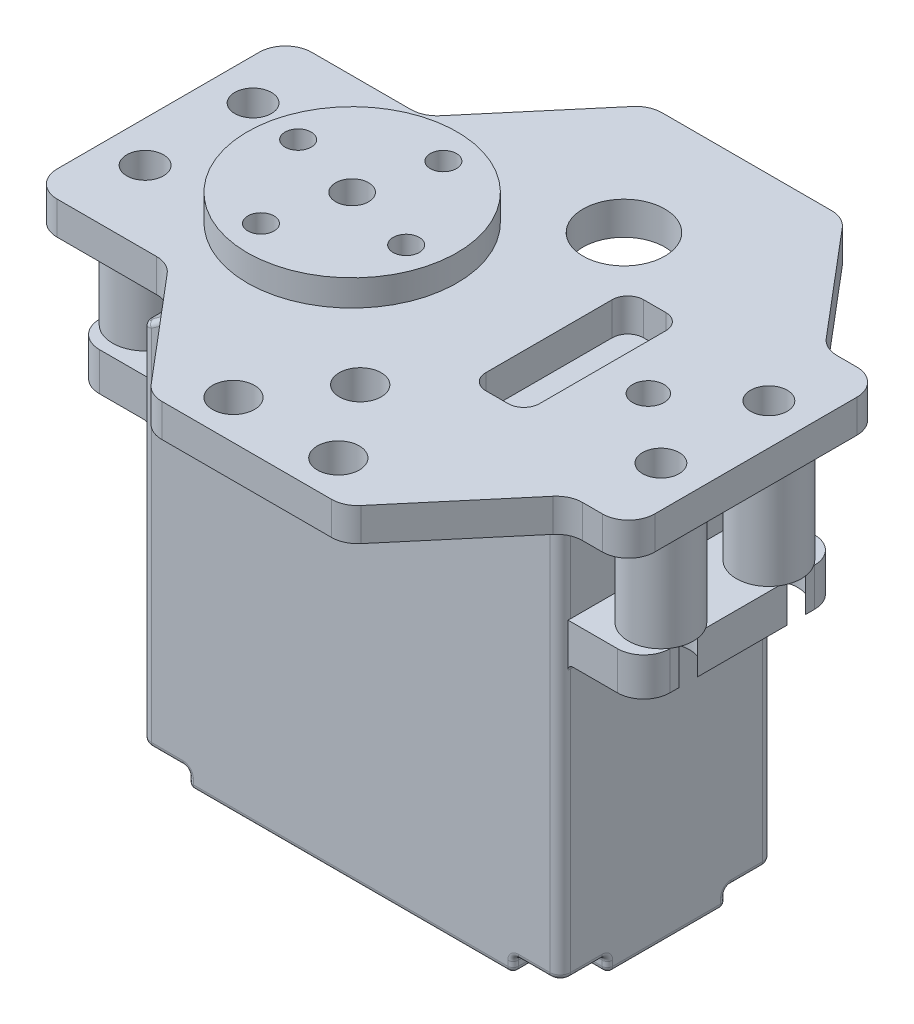
SolidWorks part; units mm, degrees
ref_plane "前基準面" through (0, 0, 0) normal (0, 0, 1) x (1, 0, 0)
ref_plane "上基準面" through (0, 0, 0) normal (0, 1, 0) x (1, 0, 0)
ref_plane "右基準面" through (0, 0, 0) normal (1, 0, 0) x (0, 0, -1)
sketch "草圖1" plane through (0, 0, 0) normal (0, 1, 0) x (1, 0, 0)
  line L0 (0, 23.4065) -> (0, -21.6093) construction
  line L1 (-8.0903, 23.85) -> (8.0903, 23.85)
  line L2 (9.999, 22.9646) -> (18.411, 13.0204)
  line L3 (20.3197, 12.135) -> (22.21, 12.135)
  line L4 (24.71, 9.635) -> (24.71, -9.635)
  line L5 (24.71, 0) -> (-24.71, 0) construction
  line L6 (-8.0903, -23.85) -> (8.0903, -23.85)
  line L7 (20.3197, -12.135) -> (22.21, -12.135)
  line L8 (9.999, -22.9646) -> (18.411, -13.0204)
  line L9 (-9.999, -22.9646) -> (-18.411, -13.0204)
  line L10 (-20.3197, -12.135) -> (-29.79, -12.135)
  line L11 (-32.29, 9.635) -> (-32.29, -9.635)
  line L12 (-20.3197, 12.135) -> (-29.79, 12.135)
  line L13 (-9.999, 22.9646) -> (-18.411, 13.0204)
  line L14 (5, -20.1095) -> (12.4142, -20.1095) construction
  line L15 (6.4847, -7.525) -> (8.61, -7.525)
  line L16 (4.9847, -6.025) -> (4.9847, 6.025)
  line L17 (6.4847, 7.525) -> (8.61, 7.525)
  line L18 (10.11, -6.025) -> (10.11, 6.025)
  line L19 (4.9847, -7.525) -> (10.11, 7.525) construction
  line L20 (4.9847, 7.525) -> (10.11, -7.525) construction
  arc A0 (-20.3197, 12.135) -> (-18.411, 13.0204) centre (-20.3197, 14.635) ccw
  arc A1 (-32.29, 9.635) -> (-29.79, 12.135) centre (-29.79, 9.635) cw
  arc A2 (-29.79, -12.135) -> (-32.29, -9.635) centre (-29.79, -9.635) cw
  arc A3 (-18.411, -13.0204) -> (-20.3197, -12.135) centre (-20.3197, -14.635) ccw
  arc A4 (-9.999, -22.9646) -> (-8.0903, -23.85) centre (-8.0903, -21.35) ccw
  arc A5 (8.0903, -23.85) -> (9.999, -22.9646) centre (8.0903, -21.35) ccw
  arc A6 (20.3197, -12.135) -> (18.411, -13.0204) centre (20.3197, -14.635) ccw
  arc A7 (18.411, 13.0204) -> (20.3197, 12.135) centre (20.3197, 14.635) ccw
  arc A8 (-9.999, 22.9646) -> (-8.0903, 23.85) centre (-8.0903, 21.35) cw
  arc A9 (8.0903, 23.85) -> (9.999, 22.9646) centre (8.0903, 21.35) cw
  arc A10 (22.21, 12.135) -> (24.71, 9.635) centre (22.21, 9.635) cw
  arc A11 (22.21, -12.135) -> (24.71, -9.635) centre (22.21, -9.635) ccw
  circle A12 centre (0, 12.135) radius 3.9
  arc A13 (8.61, -7.525) -> (10.11, -6.025) centre (8.61, -6.025) ccw
  arc A14 (6.4847, -7.525) -> (4.9847, -6.025) centre (6.4847, -6.025) cw
  arc A15 (4.9847, 6.025) -> (6.4847, 7.525) centre (6.4847, 6.025) cw
  arc A16 (8.61, 7.525) -> (10.11, 6.025) centre (8.61, 6.025) cw
  circle A17 centre (0, -13.0204) radius 2
  circle A18 centre (-5, -20.1095) radius 2
  circle A19 centre (5, -20.1095) radius 2
  point P3 (7.5474, 0)
  point P14 (0, -23.85)
  point P19 (0, 23.85)
  point P25 (-19.16, 12.135)
  point P30 (-32.29, -12.135)
  point P33 (-19.16, -12.135)
  point P36 (-9.25, -23.85)
  point P39 (9.25, -23.85)
  point P42 (19.16, -12.135)
  point P45 (19.16, 12.135)
  point P50 (9.25, 23.85)
  point P53 (24.71, 12.135)
  point P56 (24.71, -12.135)
  point P78 (0, 0)
  point P80 (4.9597, -20.1095)
  point P82 (4.9847, -20.09)
  dimension "D7" = 2.5
  dimension "D8" = 7.8
  dimension "D11" = 1.5
  dimension "D12" = 4
  dimension "D1" = 57
  dimension "D2" = 47.7
  dimension "D3" = 24.27
  dimension "D4" = 5.55
  dimension "D5" = 13.13
  dimension "D6" = 18.5
  dimension "D9" = 14.6
  dimension "D10" = 15.05
extrude "填料-伸長1" add sketch "草圖1" along normal blind 3.05 and the other way blind 0.1
sketch "草圖2" plane through (0, -0.1, 0) normal (0, -1, 0) x (1, 0, 0)
  line L0 (24.71, 9.635) -> (24.71, -9.635) construction
  line L1 (-32.29, -9.635) -> (-32.29, 9.635) construction
  line L2 (-25.2838, 0) -> (21.674, 0) construction
  circle A0 centre (20.81, 5.15) radius 3.1
  circle A1 centre (20.81, -5.15) radius 3.1
  circle A2 centre (-28.39, 5.15) radius 3.1
  circle A3 centre (-28.39, -5.15) radius 3.1
  dimension "D1" = 6.2
  dimension "D2" = 3.9
  dimension "D3" = 3.9
  dimension "D4" = 10.3
extrude "填料-伸長2" add sketch "草圖2" along normal blind 10
sketch "草圖3" plane through (0, -10.1, 0) normal (0, -1, 0) x (1, 0, 0)
  line L0 (-32.29, 0) -> (24.71, 0) construction
  line L1 (-28.4995, -9.4) -> (20.9195, -9.4)
  line L2 (-30.9995, -6.9) -> (-30.9995, -6.0177)
  line L3 (-28.4995, 9.4) -> (20.9195, 9.4)
  line L4 (23.4195, -6.9) -> (23.4195, -6.0177)
  line L5 (-30.9995, -9.4) -> (23.4195, 9.4) construction
  line L6 (-30.9995, 9.4) -> (23.4195, -9.4) construction
  line L7 (-32.29, -9.635) -> (-32.29, 9.635) construction
  line L8 (24.71, 9.635) -> (24.71, -9.635) construction
  line L9 (-3.79, 0) -> (-3.79, -23.85) construction
  line L10 (8.0903, -23.85) -> (-8.0903, -23.85) construction
  line L11 (23.4195, 6.0177) -> (23.4195, 6.9)
  line L12 (-30.9995, 6.0177) -> (-30.9995, 6.9)
  line L13 (-30.9995, -4.2823) -> (-30.9995, 4.2823)
  line L14 (23.4195, -4.2823) -> (23.4195, 4.2823)
  arc A0 (-30.9995, 4.2823) -> (-30.9995, 6.0177) centre (-28.39, 5.15) ccw
  arc A1 (23.4195, 6.0177) -> (23.4195, 4.2823) centre (20.81, 5.15) ccw
  arc A2 (23.4195, -4.2823) -> (23.4195, -6.0177) centre (20.81, -5.15) ccw
  arc A3 (-30.9995, -6.0177) -> (-30.9995, -4.2823) centre (-28.39, -5.15) ccw
  arc A4 (20.9195, -9.4) -> (23.4195, -6.9) centre (20.9195, -6.9) ccw
  arc A5 (-28.4995, -9.4) -> (-30.9995, -6.9) centre (-28.4995, -6.9) cw
  arc A6 (-30.9995, 6.9) -> (-28.4995, 9.4) centre (-28.4995, 6.9) cw
  arc A7 (20.9195, 9.4) -> (23.4195, 6.9) centre (20.9195, 6.9) cw
  point P0 (-3.79, 0)
  dimension "D2" = 5.5
  dimension "D3" = 2.5
  dimension "D1" = 18.8
extrude "填料-伸長3" add sketch "草圖3" along normal blind 3.65
sketch "草圖5" plane through (0, -13.75, 0) normal (0, -1, 0) x (1, 0, 0)
  line L0 (20.9195, 9.4) -> (-28.4995, 9.4) construction
  line L1 (-3.79, 9.4) -> (-3.79, -9.4) construction
  line L2 (-28.4995, -9.4) -> (20.9195, -9.4) construction
  line L3 (-85.4185, 0) -> (23.4195, 0) construction
  line L5 (23.4195, -4.2823) -> (23.4195, 4.2823) construction
  line L7 (-22.79, -10.15) -> (15.21, -10.15)
  line L8 (-23.79, -9.15) -> (-23.79, 9.15)
  line L9 (-22.79, 10.15) -> (15.21, 10.15)
  line L10 (16.21, -9.15) -> (16.21, 9.15)
  line L11 (-23.79, -10.15) -> (16.21, 10.15) construction
  line L12 (-23.79, 10.15) -> (16.21, -10.15) construction
  arc A0 (15.21, -10.15) -> (16.21, -9.15) centre (15.21, -9.15) ccw
  arc A1 (-22.79, -10.15) -> (-23.79, -9.15) centre (-22.79, -9.15) cw
  arc A2 (-23.79, 9.15) -> (-22.79, 10.15) centre (-22.79, 9.15) cw
  arc A3 (15.21, 10.15) -> (16.21, 9.15) centre (15.21, 9.15) cw
  point P6 (-3.79, 0)
  point P9 (-30.9995, 0)
  dimension "D3" = 1
  dimension "D1" = 20.3
  dimension "D2" = 40
extrude "填料-伸長4" add sketch "草圖5" along normal blind 27.57 and the other way blind 12.45
sketch "草圖6" plane through (0, -41.32, 0) normal (0, -1, 0) x (1, 0, 0)
  line L0 (11.71, 10.15) -> (11.71, 8.15)
  line L1 (15.21, 10.15) -> (-22.79, 10.15) construction
  line L2 (14.21, 5.65) -> (16.21, 5.65)
  line L3 (16.21, -9.15) -> (16.21, 9.15) construction
  line L4 (-23.79, 0) -> (16.21, 0) construction
  line L5 (-23.79, 9.15) -> (-23.79, -9.15) construction
  line L6 (16.21, -9.15) -> (16.21, 9.15) construction
  line L7 (11.71, -10.15) -> (11.71, -8.15)
  line L8 (-3.79, 10.15) -> (-3.79, -10.15) construction
  line L9 (-22.79, -10.15) -> (15.21, -10.15) construction
  line L10 (14.21, -5.65) -> (16.21, -5.65)
  line L11 (-19.29, -10.15) -> (-19.29, -8.15)
  line L12 (-21.79, -5.65) -> (-23.79, -5.65)
  line L13 (-19.29, 10.15) -> (-19.29, 8.15)
  line L14 (-21.79, 5.65) -> (-23.79, 5.65)
  line L15 (16.21, 5.65) -> (16.21, 9.15)
  line L16 (-19.29, 10.15) -> (-22.79, 10.15)
  line L17 (-23.79, -5.65) -> (-23.79, -9.15)
  line L18 (11.71, -10.15) -> (15.21, -10.15)
  line L19 (16.21, -9.15) -> (16.21, 9.15)
  line L20 (15.21, 10.15) -> (-22.79, 10.15)
  line L21 (-23.79, 9.15) -> (-23.79, -9.15)
  line L22 (-22.79, -10.15) -> (15.21, -10.15)
  line L23 (16.21, -9.15) -> (16.21, -5.65)
  line L24 (15.21, 10.15) -> (11.71, 10.15)
  line L25 (-23.79, 9.15) -> (-23.79, 5.65)
  line L26 (-22.79, -10.15) -> (-19.29, -10.15)
  arc A0 (11.71, 8.15) -> (14.21, 5.65) centre (14.21, 8.15) ccw
  arc A1 (11.71, -8.15) -> (14.21, -5.65) centre (14.21, -8.15) cw
  arc A2 (-19.29, -8.15) -> (-21.79, -5.65) centre (-21.79, -8.15) ccw
  arc A3 (-19.29, 8.15) -> (-21.79, 5.65) centre (-21.79, 8.15) cw
  arc A8 (15.21, -10.15) -> (16.21, -9.15) centre (15.21, -9.15) ccw
  arc A9 (16.21, 9.15) -> (15.21, 10.15) centre (15.21, 9.15) ccw
  arc A10 (-22.79, 10.15) -> (-23.79, 9.15) centre (-22.79, 9.15) ccw
  arc A11 (-23.79, -9.15) -> (-22.79, -10.15) centre (-22.79, -9.15) ccw
  arc A12 (15.21, -10.15) -> (16.21, -9.15) centre (15.21, -9.15) ccw
  arc A13 (16.21, 9.15) -> (15.21, 10.15) centre (15.21, 9.15) ccw
  arc A14 (-22.79, 10.15) -> (-23.79, 9.15) centre (-22.79, 9.15) ccw
  arc A15 (-23.79, -9.15) -> (-22.79, -10.15) centre (-22.79, -9.15) ccw
  point P9 (11.71, 5.65)
  dimension "D3" = 2.5
  dimension "D1" = 4.5
  dimension "D2" = 4.5
  dimension "D4" = 0
extrude "除料-伸長1" cut sketch "草圖6" against normal blind 1.5
sketch "草圖9" plane through (0, 0, 10.15) normal (0, 0, 1) x (1, 0, 0)
  line L0 (-18.29, -1.3) -> (-23.79, -5.2131)
  line L1 (15.21, -1.3) -> (-22.79, -1.3) construction
  line L2 (-23.79, -1.3) -> (-23.79, -10.1) construction
  line L3 (-23.79, -5.2131) -> (-23.79, -1.3)
  line L4 (-23.79, -1.3) -> (-18.29, -1.3)
  dimension "D1" = 5.5
  dimension "D2" = 6.75
extrude "除料-伸長3" cut sketch "草圖9" against normal through all
fillet "圓角1" radius 0.5 65 edges at (-23.782, -13.75, 9.276) (-23.782, -13.75, -9.276) (16.202, -13.75, -9.276) (16.202, -13.75, 9.276) (-23.79, -40.57, -5.65) (-23.79, -13.75, 0) (-23.79, -40.57, 5.65) (16.21, -40.57, 5.65) (16.21, -13.75, 0) (16.21, -40.57, -5.65) (15.9171, -39.82, 9.8571) (16.21, -39.82, 7.4) (15.21, -39.82, 5.65) (12.4422, -39.82, 6.3822) (11.71, -39.82, 9.15) (11.71, -39.82, -9.15) (12.4422, -39.82, -6.3822) (15.21, -39.82, -5.65) (16.21, -39.82, -7.4) (15.9171, -39.82, -9.8571) (-19.29, -39.82, 9.15) (-20.0222, -39.82, 6.3822) (-22.79, -39.82, 5.65) (-23.79, -39.82, 7.4) (-23.4971, -39.82, 9.8571) (13.46, -39.82, 10.15) (11.71, -40.57, 10.15) (-19.29, -40.57, 10.15) (-21.04, -39.82, 10.15) (-19.29, -40.57, -10.15) (11.71, -40.57, -10.15) (13.46, -39.82, -10.15) (-23.4971, -39.82, -9.8571) (-23.79, -39.82, -7.4) (-22.79, -39.82, -5.65) (-20.0222, -39.82, -6.3822) (-19.29, -39.82, -9.15) (-21.04, -39.82, -10.15) (-3.79, -41.32, 10.15) (11.71, -41.32, 9.15) (12.4422, -41.32, 6.3822) (15.21, -41.32, 5.65) (16.21, -41.32, 0) (15.21, -41.32, -5.65) (12.4422, -41.32, -6.3822) (11.71, -41.32, -9.15) (-3.79, -41.32, -10.15) (-19.29, -41.32, -9.15) (-20.0222, -41.32, -6.3822) (-22.79, -41.32, -5.65) (-23.79, -41.32, 0) (-22.79, -41.32, 5.65) (-20.0222, -41.32, 6.3822) (-19.29, -41.32, 9.15) (-23.79, -5.2131, 0) (-23.4971, -5.0047, -9.8571) (-20.54, -2.9008, -10.15) (-20.54, -2.9008, 10.15) (-23.4971, -5.0047, 9.8571) (15.9171, -1.3, -9.8571) (16.21, -1.3, 0) (15.9171, -1.3, 9.8571) (-1.54, -1.3, 10.15) (-18.29, -1.3, 0) (-1.54, -1.3, -10.15)
sketch "草圖11" plane through (0, 3.05, 0) normal (0, 1, 0) x (1, 0, 0)
  line L0 (-32.29, 9.635) -> (-32.29, -9.635) construction
  circle A0 centre (-13.79, 0) radius 10
  circle A1 centre (-13.79, 0) radius 1.575
  circle A2 centre (-13.79, 0) radius 7.15 construction
  circle A3 centre (-12.0167, 6.9266) radius 1.25
  circle A4 centre (-13.79, 0) radius 7.15 construction
  circle A5 centre (-6.8634, -1.7733) radius 1.25
  circle A6 centre (-13.79, 0) radius 7.15 construction
  circle A7 centre (-15.5633, -6.9266) radius 1.25
  circle A8 centre (-13.79, 0) radius 7.15 construction
  circle A9 centre (-20.7166, 1.7733) radius 1.25
  point P20 (-13.79, 0)
  dimension "D1" = 20
  dimension "D3" = 3.15
  dimension "D5" = 14.3
  dimension "D6" = 2.5
  dimension "D2" = 18.5
  dimension "D4" = 4
extrude "填料-伸長5" add sketch "草圖11" along normal blind 2.5
sketch "草圖12" plane through (0, 3.05, 0) normal (0, 1, 0) x (1, 0, 0)
  line L0 (24.71, -9.635) -> (24.71, 9.635) construction
  circle A0 centre (14.46, 0) radius 1.5
  dimension "D1" = 3
  dimension "D2" = 10.25
extrude "除料-伸長4" cut sketch "草圖12" against normal up to next
sketch "草圖13" plane through (0, 3.05, 0) normal (0, 1, 0) x (1, 0, 0)
  circle A0 centre (20.81, -5.15) radius 1.75
  circle A1 centre (20.81, 5.15) radius 1.75
  circle A2 centre (-28.39, -5.15) radius 1.75
  circle A3 centre (-28.39, 5.15) radius 1.75
  dimension "D1" = 3.5
extrude "除料-伸長5" cut sketch "草圖13" against normal through all
